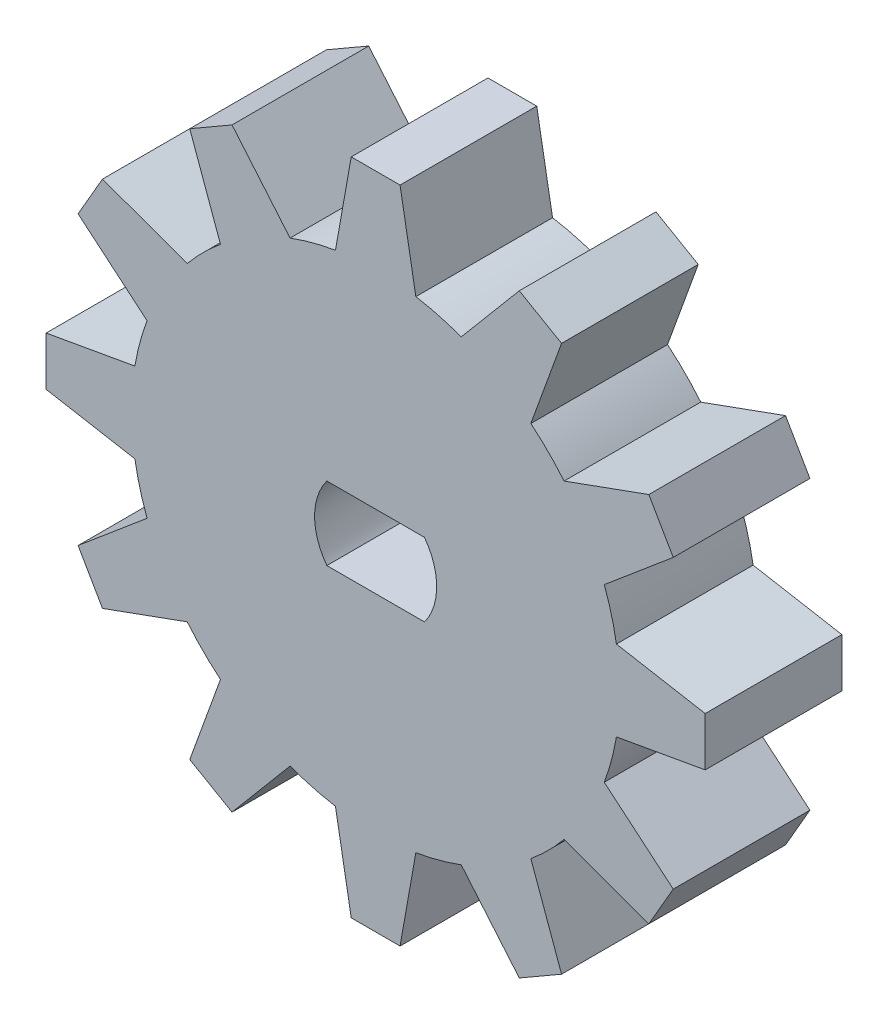
SolidWorks part; units mm, degrees
ref_plane "Front Plane" through (0, 0, 0) normal (0, 0, 1) x (1, 0, 0)
ref_plane "Top Plane" through (0, 0, 0) normal (0, 1, 0) x (1, 0, 0)
ref_plane "Right Plane" through (0, 0, 0) normal (1, 0, 0) x (0, 0, -1)
sketch "Sketch1" plane through (0, 0, 0) normal (0, 0, 1) x (1, 0, 0)
  circle A0 centre (0, 0) radius 10
  dimension "D1" = 20
extrude "Boss-Extrude1" add sketch "Sketch1" along normal blind 5.6
sketch "Sketch3" plane through (0, 0, 0) normal (0, 0, 1) x (1, 0, 0)
  line L0 (0, -13.5) -> (0, 13.5) construction
  line L1 (-1, 13.5) -> (1, 13.5)
  line L2 (-1, 13.5) -> (-1.8, 9)
  line L3 (-1.8, 9) -> (1.8, 9)
  line L4 (1.8, 9) -> (1, 13.5)
  point P3 (0, 0)
  point P4 (0, 9)
  point P6 (0, 13.5)
  dimension "D1" = 13.5
  dimension "D2" = 3.6
  dimension "D3" = 2
  dimension "D4" = 9
extrude "Boss-Extrude2" add sketch "Sketch3" along normal blind 5.6
ref_axis "Axis2" through (0, 0, 5.6) along (0, 0, -1)
pattern_circular "CirPattern1" count 12 every 30 about axis through (0, 0, 0) along (0, 0, 1) of "Boss-Extrude2"
sketch "Sketch4" plane through (0, 0, 0) normal (0, 0, 1) x (1, 0, 0)
  line L1 (-2, -1.5) -> (2, -1.5)
  line L2 (-2, 1.5) -> (2, 1.5)
  arc A1 (2, -1.5) -> (2, 1.5) centre (0, 0) ccw
  circle A2 centre (0, 0) radius 1.5 construction
  arc A3 (-2, 1.5) -> (-2, -1.5) centre (0, 0) ccw
  point P5 (0, -1.5)
  point P8 (0, 1.5)
  dimension "D1" = 4
  dimension "D2" = 2.5
extrude "Cut-Extrude1" cut sketch "Sketch4" along normal blind 7
